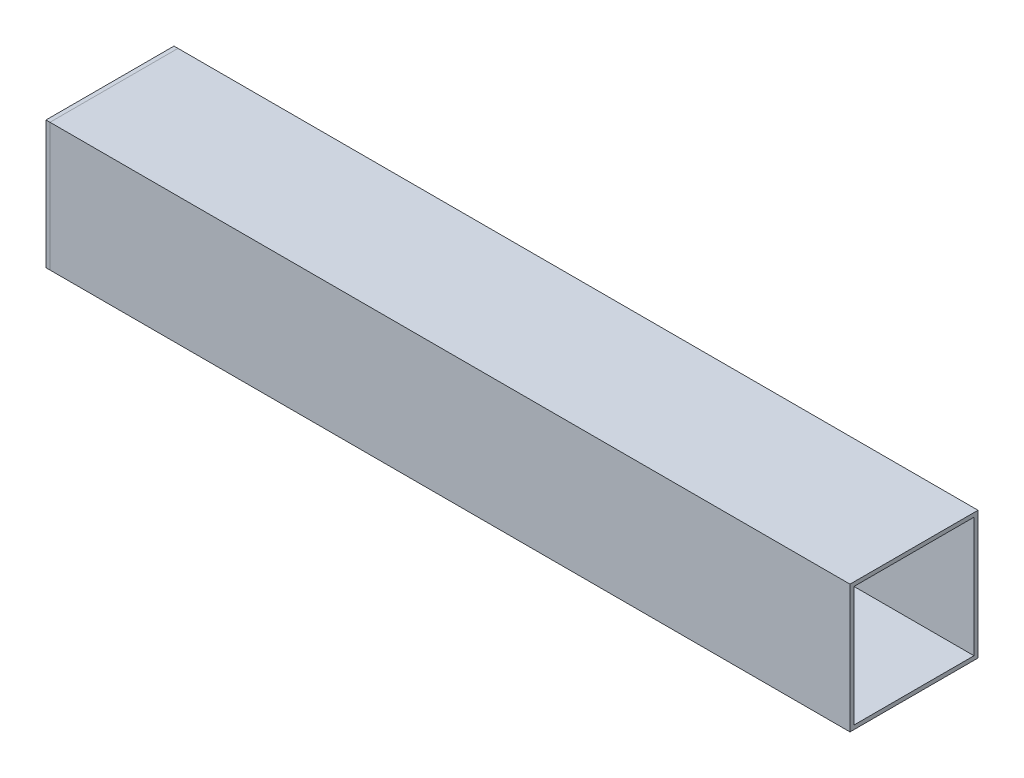
SolidWorks part; units mm, degrees
ref_plane "Front Plane" through (0, 0, 0) normal (0, 0, 1) x (1, 0, 0)
ref_plane "Top Plane" through (0, 0, 0) normal (0, 1, 0) x (1, 0, 0)
ref_plane "Right Plane" through (0, 0, 0) normal (1, 0, 0) x (0, 0, -1)
sketch "Sketch1" plane through (0, 0, 0) normal (1, 0, 0) x (0, 0, -1)
  line L0 (-98.425, 3.175) -> (-98.425, 98.425)
  line L1 (0, 0) -> (-101.6, 0)
  line L2 (0, 0) -> (0, 101.6)
  line L3 (0, 101.6) -> (-101.6, 101.6)
  line L4 (-101.6, 0) -> (-101.6, 101.6)
  line L5 (-3.175, 98.425) -> (-98.425, 98.425)
  line L6 (-3.175, 3.175) -> (-3.175, 98.425)
  line L7 (-3.175, 3.175) -> (-98.425, 3.175)
  dimension "D1" = 101.6
  dimension "D2" = 101.6
  dimension "D3" = 3.175
extrude "Boss-Extrude1" add sketch "Sketch1" along normal blind 635
sketch "Sketch2" plane through (0, 0, 0) normal (-1, 0, 0) x (0, 0, 1)
  line L4 (0, 101.6) -> (0, 0)
  line L5 (0, 0) -> (101.6, 0)
  line L6 (101.6, 0) -> (101.6, 101.6)
  line L7 (101.6, 101.6) -> (0, 101.6)
  line L8 (0, 101.6) -> (0, 0)
  line L9 (0, 0) -> (101.6, 0)
  line L10 (101.6, 0) -> (101.6, 101.6)
  line L11 (101.6, 101.6) -> (0, 101.6)
  dimension "D1" = 0
extrude "Boss-Extrude2" add sketch "Sketch2" along normal blind 3.175 separate body
